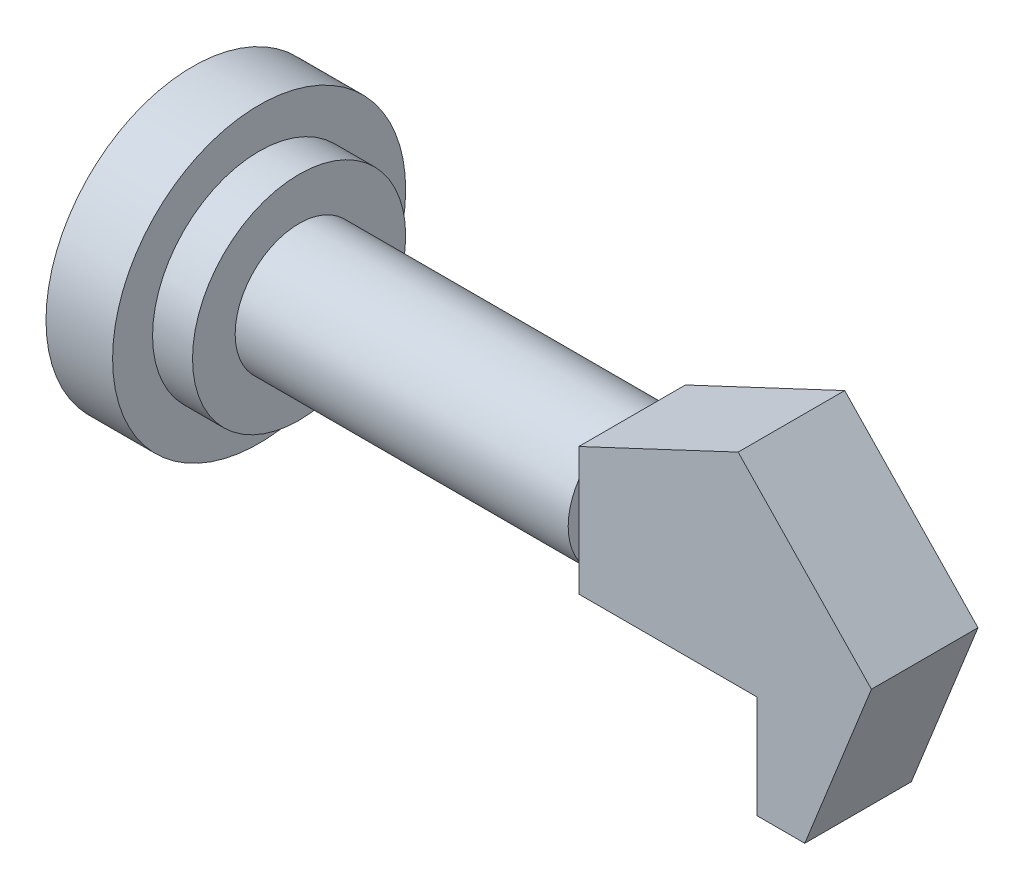
SolidWorks part; units mm, degrees
ref_plane "Спереди" through (0, 0, 0) normal (0, 0, 1) x (1, 0, 0)
ref_plane "Сверху" through (0, 0, 0) normal (0, 1, 0) x (1, 0, 0)
ref_plane "Справа" through (0, 0, 0) normal (1, 0, 0) x (0, 0, -1)
other "Configuration Table"
sketch "Эскиз1" plane through (0, 0, 0) normal (0, 0, 1) x (1, 0, 0)
  line L0 (0, 0) -> (5, 0)
  line L1 (0, 0) -> (0, 22)
  line L2 (0, 22) -> (5, 22)
  line L3 (5, 0) -> (5, 22)
  line L4 (5, 19) -> (8, 19)
  line L5 (5, 19) -> (5, 3)
  line L6 (5, 3) -> (8, 3)
  line L7 (8, 19) -> (8, 3)
  line L8 (8, 15.8) -> (33, 15.8)
  line L9 (8, 15.8) -> (8, 6.2)
  line L10 (8, 6.2) -> (33, 6.2)
  line L11 (33, 15.8) -> (33, 6.2)
  line L16 (0, 11) -> (46.3881, 11) construction
  line L17 (33, 15.8) -> (44.9581, 21.4143)
  line L18 (44.9581, 21.4143) -> (54.9646, 11)
  line L19 (54.9646, 11) -> (49.9614, -1.5174)
  line L20 (49.9614, -1.5174) -> (46.3881, -1.5174)
  line L21 (46.3881, -1.5174) -> (46.3881, 6.2)
  line L22 (46.3881, 6.2) -> (33, 6.2)
  dimension "D1" = 22
  dimension "D2" = 5
  dimension "D3" = 3
  dimension "D4" = 25
  dimension "D5" = 3
  dimension "D6" = 3.2
  dimension "D7" = 3
  dimension "D8" = 3.2
  dimension "D9" = 13.3881
  dimension "D10" = 7.7174
  dimension "D11" = 13.2104
  dimension "D12" = 14.4426
  dimension "D13" = 13.4803
  dimension "D14" = 12.2805
  dimension "D15" = 108.706
revolve "Повернуть1" add sketch "Эскиз1" angle 360 about L16 region at (2.5, 5.5, 0) region at (6.5, 7, 0) region at (20.5, 8.6, 0)
extrude "Бобышка-Вытянуть1" add sketch "Эскиз1<3>" along normal blind 4 and the other way blind 4 contours L22 L21 L20 L19 L18 L17 L11 region at (43.9393, 10.9215, 0)
sketch "Эскиз1<3>" plane through (0, 0, 0) normal (0, 0, 1) x (1, 0, 0) same geometry as "Эскиз1"
